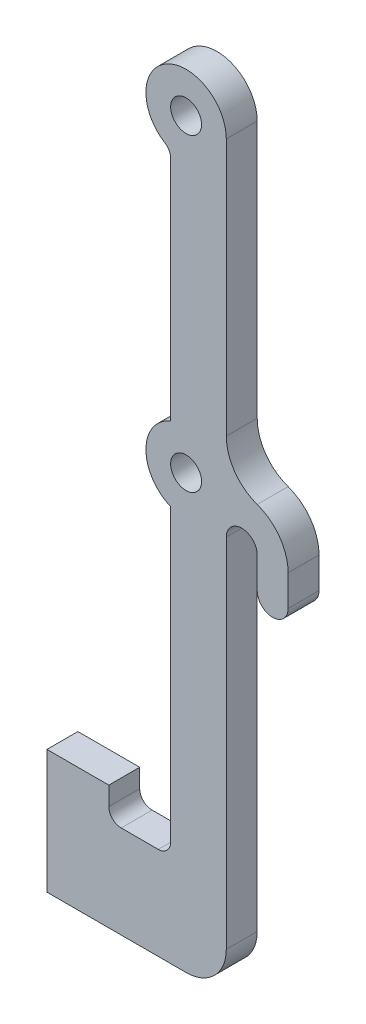
SolidWorks part; units mm, degrees
ref_plane "Front Plane" through (0, 0, 0) normal (0, 0, 1) x (1, 0, 0)
ref_plane "Top Plane" through (0, 0, 0) normal (0, 1, 0) x (1, 0, 0)
ref_plane "Right Plane" through (0, 0, 0) normal (1, 0, 0) x (0, 0, -1)
sketch "Sketch1" plane through (0, 0, 0) normal (0, 0, 1) x (1, 0, 0)
  line L0 (8.255, 0) -> (8.255, -144.145)
  line L1 (-3.175, -7.62) -> (-3.175, -55.88)
  line L2 (-5.715, -133.35) -> (-13.335, -133.35)
  line L3 (-15.875, -130.81) -> (-15.875, -127)
  line L4 (-15.875, -127) -> (-28.575, -127)
  line L5 (-28.575, -127) -> (-28.575, -152.4)
  line L6 (0, 0) -> (0, -144.145) construction
  line L7 (0, -152.4) -> (-28.575, -152.4)
  line L8 (-3.175, -71.12) -> (-3.175, -130.81)
  arc A0 (8.255, 0) -> (-3.175, -7.62) centre (0, 0) ccw
  circle A1 centre (0, 0) radius 3.175
  arc A3 (-13.335, -133.35) -> (-15.875, -130.81) centre (-13.335, -130.81) cw
  arc A4 (-5.715, -133.35) -> (-3.175, -130.81) centre (-5.715, -130.81) ccw
  circle A5 centre (0, -144.145) radius 3.175 construction
  arc A6 (8.255, -144.145) -> (0, -152.4) centre (0, -144.145) cw
  circle A7 centre (0, -63.5) radius 3.175
  arc A8 (-3.175, -55.88) -> (-3.175, -71.12) centre (0, -63.5) ccw
  circle A9 centre (0, -63.5) radius 8.255 construction
  dimension "D1" = 16.51
  dimension "D2" = 2.54
  dimension "D4" = 6.35
  dimension "D7" = 6.35
  dimension "D3" = 12.7
  dimension "D9" = 63.5
  dimension "D5" = 152.4
  dimension "D6" = 6.35
  dimension "D8" = 25.4
  dimension "D12" = 12.7
  dimension "D13" = 6.35
extrude "Boss-Extrude1" add sketch "Sketch1" along normal mid plane 6.35 contours A8 L8 A4 L2 A3 L3 L4 L5 L7 A6 L0 region at (-2.3168, -87.4338, 0)
fillet "Fillet1" radius 2.54 1 edges at (-3.175, -7.62, 0)
sketch "Sketch2" plane through (0, 0, 3.175) normal (0, 0, 1) x (1, 0, 0)
  line L1 (14.605, -70.8224) -> (14.605, -77.1724)
  line L2 (8.255, 0) -> (8.255, -144.145) construction
  line L3 (20.955, -77.1724) -> (20.955, -70.8224)
  line L4 (8.255, -52.8619) -> (8.255, -70.8224)
  arc A0 (14.605, -70.8224) -> (8.255, -70.8224) centre (11.43, -70.8224) ccw
  arc A2 (14.605, -77.1724) -> (20.955, -77.1724) centre (17.78, -77.1724) ccw
  arc A3 (20.955, -70.8224) -> (14.605, -61.8422) centre (11.43, -70.8224) ccw
  arc A4 (14.605, -61.8422) -> (8.255, -52.8619) centre (17.78, -52.8619) cw
  point P6 (0, 0)
  point P7 (8.255, -70.8224)
  dimension "D3" = 3.175
  dimension "D4" = 3.175
  dimension "D1" = 6.35
  dimension "D2" = 6.35
extrude "Boss-Extrude2" add sketch "Sketch2" against normal blind 6.35
